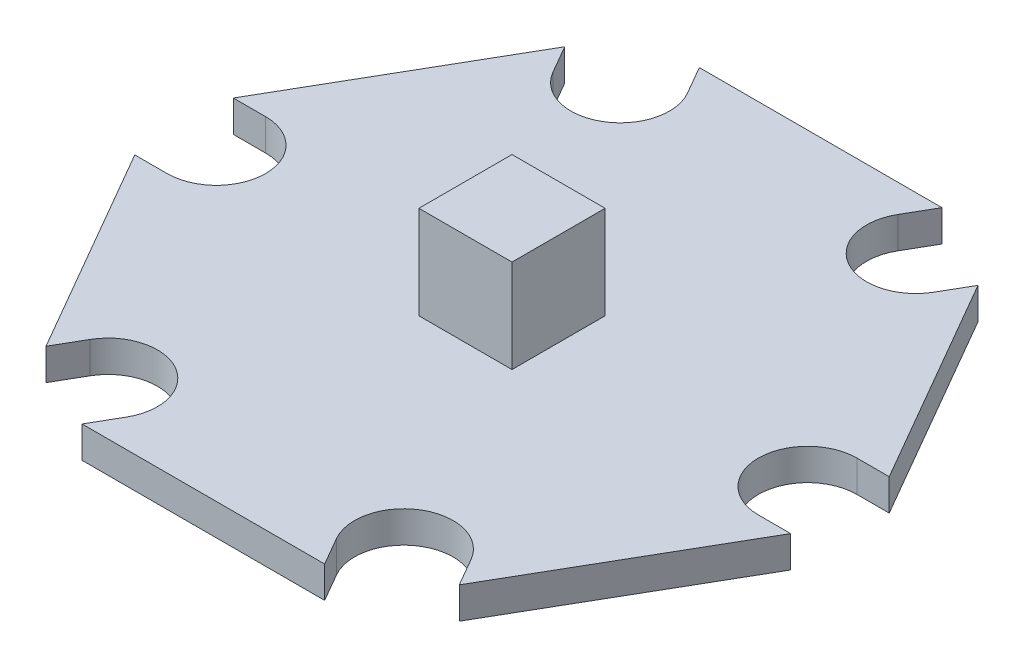
SolidWorks part; units mm, degrees
ref_plane "Front Plane" through (0, 0, 0) normal (0, 0, 1) x (1, 0, 0)
ref_plane "Top Plane" through (0, 0, 0) normal (0, 1, 0) x (1, 0, 0)
ref_plane "Right Plane" through (0, 0, 0) normal (1, 0, 0) x (0, 0, -1)
sketch "Sketch1" plane through (0, 0, 0) normal (0, 1, 0) x (1, 0, 0)
  line L7 (5.7412, 9.9441) -> (-5.7412, 9.9441)
  line L8 (-5.7412, 9.9441) -> (-11.4825, 0)
  line L9 (-11.4825, 0) -> (-5.7412, -9.9441)
  line L10 (-5.7412, -9.9441) -> (5.7412, -9.9441)
  line L11 (5.7412, -9.9441) -> (11.4825, 0)
  line L12 (11.4825, 0) -> (5.7412, 9.9441)
  circle A1 centre (0, 0) radius 9.9441 construction
extrude "Boss-Extrude1" add sketch "Sketch1" along normal blind 1.016
sketch "Sketch2" plane through (0, 1.016, 0) normal (0, 1, 0) x (1, 0, 0)
  line L6 (9.525, 1.5875) -> (13.1378, 1.5875)
  line L12 (9.525, -1.5875) -> (13.1378, -1.5875)
  line L13 (13.1378, 1.5875) -> (13.1378, -1.5875)
  arc A1 (9.525, 1.5875) -> (9.525, -1.5875) centre (9.525, 0) ccw
  dimension "D1" = 9.525
extrude "Cut-Extrude1" cut sketch "Sketch2" against normal blind 1.016
ref_axis "Axis1" through (0, 4.2168, 0) along (0, -1, 0)
pattern_circular "CirPattern1" count 6 every 60 about axis through (0, 4.2168, 0) along (0, -1, 0) of "Cut-Extrude1"
sketch "Sketch3" plane through (0, 1.016, 0) normal (0, 1, 0) x (1, 0, 0)
  line L1 (-1.5, -1.5) -> (-1.5, 1.5)
  line L2 (-1.5, -1.5) -> (1.5, -1.5)
  line L3 (-1.5, 1.5) -> (1.5, 1.5)
  line L4 (1.5, -1.5) -> (1.5, 1.5)
  line L6 (-1.5, 1.5) -> (-0.0012, 0.0012) construction
  point P9 (0, 0)
  dimension "D1" = 3
  dimension "D2" = 3
extrude "Boss-Extrude2" add sketch "Sketch3" along normal blind 3
